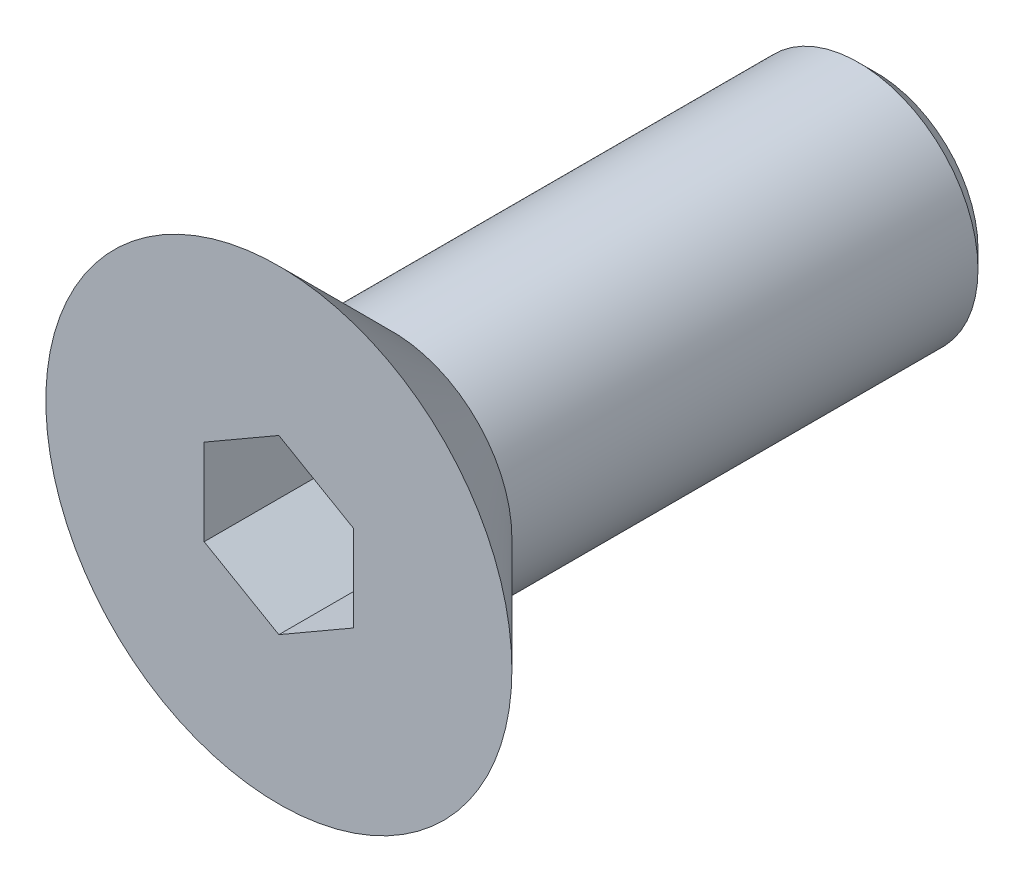
SolidWorks part; units mm, degrees
ref_plane "Front Plane" through (0, 0, 0) normal (0, 0, 1) x (1, 0, 0)
ref_plane "Top Plane" through (0, 0, 0) normal (0, 1, 0) x (1, 0, 0)
ref_plane "Right Plane" through (0, 0, 0) normal (1, 0, 0) x (0, 0, -1)
sketch "Sketch1" plane through (0, 0, 0) normal (0, 0, 1) x (1, 0, 0)
  circle A0 centre (0, 0) radius 4
  dimension "D1" = 8
extrude "Boss-Extrude1" add sketch "Sketch1" along normal blind 2.3
sketch "Sketch2" plane through (0, 0, 0) normal (0, 0, -1) x (-1, 0, 0)
  circle A0 centre (0, 0) radius 2
  dimension "D1" = 4
extrude "Boss-Extrude2" add sketch "Sketch2" along normal blind 7.7
chamfer "Chamfer1" distance 0.3 angle 45 1 edges at (-2, 0, -7.7)
sketch "Sketch3" plane through (0, 0, 2.3) normal (0, 0, 1) x (1, 0, 0)
  line L1 (0, 1.4434) -> (-1.25, 0.7217)
  line L2 (-1.25, 0.7217) -> (-1.25, -0.7217)
  line L3 (-1.25, -0.7217) -> (0, -1.4434)
  line L4 (0, -1.4434) -> (1.25, -0.7217)
  line L5 (1.25, -0.7217) -> (1.25, 0.7217)
  line L6 (1.25, 0.7217) -> (0, 1.4434)
  circle A0 centre (0, 0) radius 1.25 construction
  dimension "D1" = 2.5
extrude "Cut-Extrude1" cut sketch "Sketch3" against normal blind 2
chamfer "Chamfer2" distance 2.4 angle 45 1 edges at (4, 0, 0)
